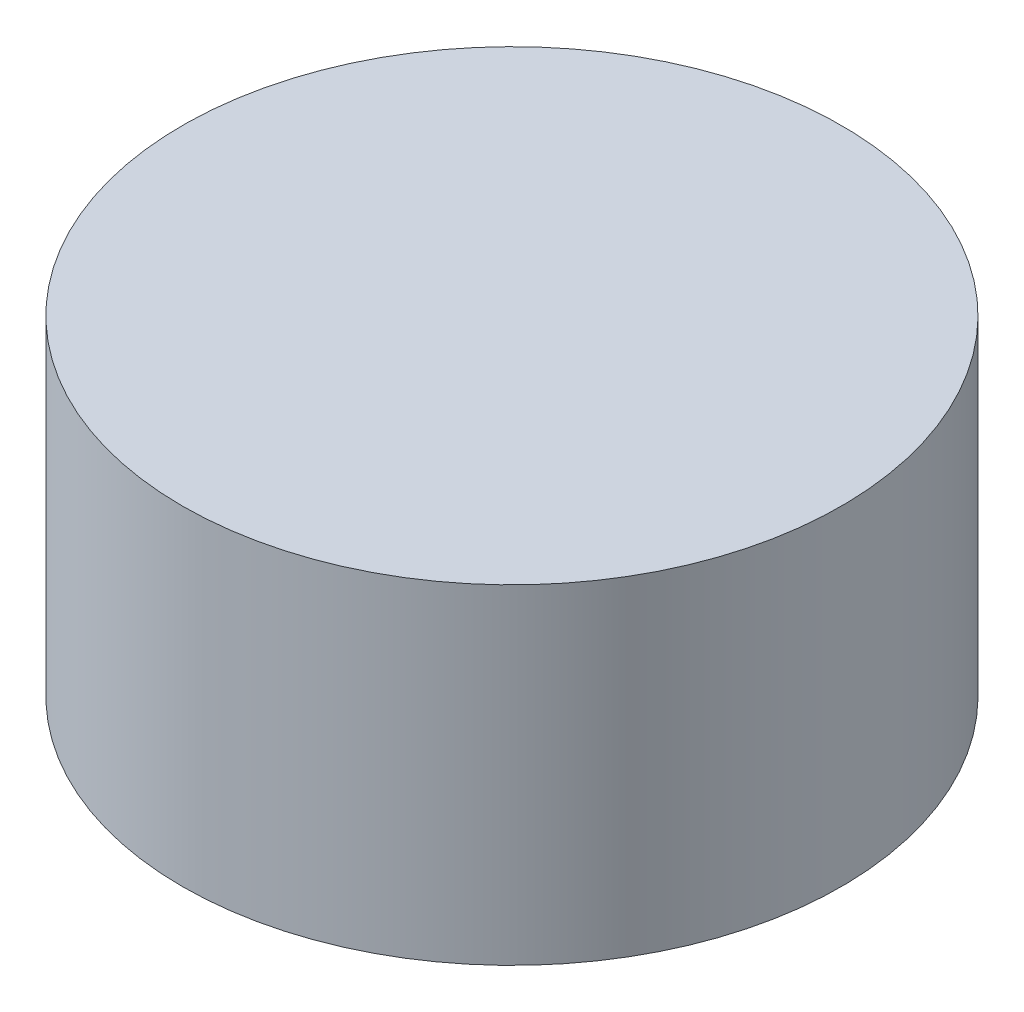
SolidWorks part; units mm, degrees
material "ABS"
ref_plane "Front Plane" through (0, 0, 0) normal (0, 0, 1) x (1, 0, 0)
ref_plane "Top Plane" through (0, 0, 0) normal (0, 1, 0) x (1, 0, 0)
ref_plane "Right Plane" through (0, 0, 0) normal (1, 0, 0) x (0, 0, -1)
sketch "Sketch1" plane through (0, 0, 0) normal (0, 1, 0) x (1, 0, 0)
  circle A0 centre (0, 0) radius 2
  dimension "D1" = 4
extrude "Boss-Extrude1" add sketch "Sketch1" along normal blind 2
